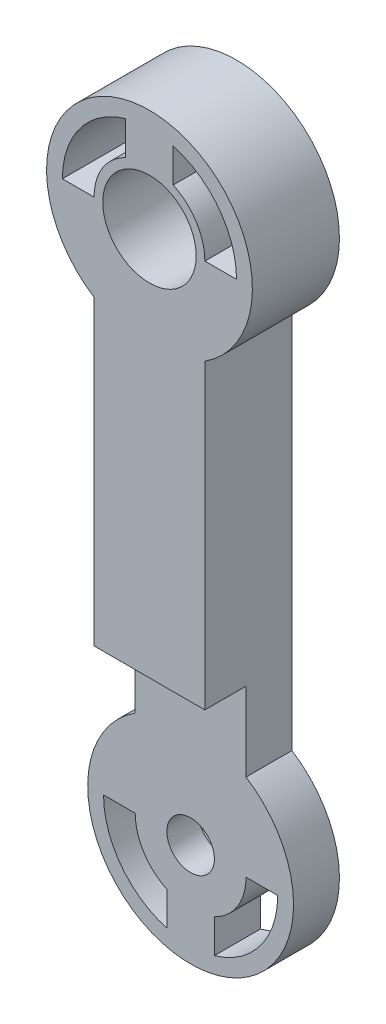
SolidWorks part; units mm, degrees
ref_plane "Front Plane" through (0, 0, 0) normal (0, 0, 1) x (1, 0, 0)
ref_plane "Top Plane" through (0, 0, 0) normal (0, 1, 0) x (1, 0, 0)
ref_plane "Right Plane" through (0, 0, 0) normal (1, 0, 0) x (0, 0, -1)
sketch "Sketch1" plane through (0, 0, 0) normal (0, 0, 1) x (1, 0, 0)
  line L0 (0, 0) -> (0, -35) construction
  line L1 (-3.5, 0) -> (-5.5, 0)
  line L2 (3.5, 0) -> (5.5, 0)
  line L3 (0, -17.5) -> (10.3868, -17.5) construction
  line L5 (-1.5, 3.1623) -> (-1.5, 5.2915)
  line L7 (1.5, 3.1623) -> (1.5, 5.2915)
  line L8 (1.5, -38.1623) -> (1.5, -40.2915)
  line L9 (-1.5, -38.1623) -> (-1.5, -40.2915)
  line L10 (3.5, -35) -> (5.5, -35)
  line L11 (-3.5, -35) -> (-5.5, -35)
  line L13 (-3.5, 0) -> (3.5, 0)
  line L14 (-3.5, 0) -> (-3.5, -35)
  line L15 (-3.5, -35) -> (3.5, -35)
  line L16 (3.5, 0) -> (3.5, -35)
  circle A0 centre (0, 0) radius 2.95
  circle A1 centre (0, 0) radius 6.5
  circle A2 centre (0, 0) radius 3.5
  circle A3 centre (0, 0) radius 5.5
  circle A4 centre (0, -35) radius 5.5
  circle A5 centre (0, -35) radius 3.5
  circle A6 centre (0, -35) radius 6.5
  circle A7 centre (0, -35) radius 2.95
  dimension "D1" = 5.9
  dimension "D2" = 13
  dimension "D3" = 11
  dimension "D4" = 7
  dimension "D5" = 35
extrude "Boss-Extrude1" add sketch "Sketch1" along normal blind 3.7 contours L14 A6 L16 A1 | A3 L16 A1 L14 | L14 A3 L16 A2 | A3 L14 A1 L16 | A6 L14 A4 L16 | A6 L16 A4 L14 | L14 A5 L16 A4 | A4 L11 L14 | A4 L16 L10 | L15 A7 A5 | L15 A7 A5 | L7 A3 L5 A2 | L1 A3 L14 | L16 A3 L2 | L13 A2 A0 | L13 A2 A0 | L8 A5 L9 A4 region at (-4.3139, -1.6382, 0) region at (-2.8919, 1.829, 0) region at (0, -3.8245, 0) region at (-3.225, -0.0783, 0) region at (-5.1348, -2.4206, 0) region at (0, -5.6156, 0) region at (0, 4.4089, 0) region at (4.3139, -1.6382, 0) region at (0, -17.5, 0) region at (0, -29.3844, 0) region at (-3.6768, -30.1401, 0) region at (0, -31.1755, 0) region at (-4.3139, -33.3618, 0) region at (0, -31.5783, 0) region at (-3.225, -35.0783, 0) region at (4.3139, -33.3618, 0) region at (0, -39.4089, 0)
sketch "Sketch2" plane through (0, 0, 0) normal (1, 0, 0) x (0, 0, -1)
  line L0 (0, 0) -> (0, -24.55) construction
  line L1 (0, -5.4772) -> (0, -29.5228) construction
  line L2 (-3.7, -5.4772) -> (-3.7, -29.5228) construction
  line L3 (-3.7, -24.55) -> (-3.1, -24.55)
  line L4 (-3.7, -24.55) -> (-3.7, -41.5)
  line L5 (-3.7, -41.5) -> (-3.1, -41.5)
  line L6 (-3.1, -24.55) -> (-3.1, -41.5)
  line L7 (-3.7, -41.5) -> (0, -41.5) construction
  dimension "D1" = 24.55
  dimension "D2" = 0.6
extrude "Cut-Extrude1" cut sketch "Sketch2" against normal blind 10 and the other way blind 10
sketch "Sketch3" plane through (0, 0, 0) normal (0, 0, -1) x (-1, 0, 0)
  circle A0 centre (0, -35) radius 2.95
  circle A1 centre (0, -35) radius 1.5
  dimension "D1" = 3
extrude "Boss-Extrude2" add sketch "Sketch3" against normal blind 3.1
sketch "Sketch4" plane through (0, 0, 0) normal (0, 0, -1) x (-1, 0, 0)
  circle A0 centre (0, -35) radius 2.5
  dimension "D1" = 5
extrude "Cut-Extrude2" cut sketch "Sketch4" against normal blind 1.5
sketch "Sketch5" plane through (0, 0, 3.1) normal (0, 0, 1) x (1, 0, 0)
  line L1 (-3.5, -24.55) -> (3.5, -24.55)
  line L2 (-3.5, -24.55) -> (-3.5, -29.5228)
  line L4 (3.5, -24.55) -> (3.5, -29.5228)
  line L5 (-5.5, -35) -> (-3.5, -35)
  line L8 (-1.5, -38.1623) -> (-1.5, -40.2915)
  line L9 (5.5, -35) -> (3.5, -35)
  line L12 (1.5, -38.1623) -> (1.5, -40.2915)
  circle A0 centre (0, -35) radius 1.5
  circle A1 centre (0, -35) radius 6.5
  circle A2 centre (0, -35) radius 3.5
  arc A3 (-5.5, -35) -> (5.5, -35) centre (0, -35) ccw
  line M2 (3.5, -35) -> (5.5, -35)
  line M4 (1.5, -40.2915) -> (1.5, -38.1623)
  arc M5 (1.5, -38.1623) -> (3.5, -35) centre (0, -35) ccw
  arc M6 (-3.5, -35) -> (-1.5, -38.1623) centre (0, -35) ccw
  line M7 (-1.5, -38.1623) -> (-1.5, -40.2915)
  line M9 (-5.5, -35) -> (-3.5, -35)
  line M10 (-3.5, -24.55) -> (-3.5, -29.5228)
  line M12 (3.5, -29.5228) -> (3.5, -24.55)
  line M13 (3.5, -24.55) -> (-3.5, -24.55)
  circle M14 centre (0, -35) radius 1.5
extrude "Boss-Extrude3" add sketch "Sketch5" along normal blind 0.4 contours A1 M12 M13 M10 | A3 A2 M2 M9 | A2 M5 M6 M14 | A3 A2 M7 M4 region at (0, -26.7003, 3.1) region at (0, -28.6838, 3.1) region at (0, -31.599, 3.1) region at (0, -39.4089, 3.1)
sketch "Sketch6" plane through (0, 0, 3.7) normal (0, 0, 1) x (1, 0, 0)
  line L0 (-1.5, 5.2915) -> (-1.5, 3.1623)
  line L2 (-3.5, -5.4772) -> (-3.5, -24.55)
  line L3 (-3.5, -24.55) -> (3.5, -24.55)
  line L4 (3.5, -5.4772) -> (3.5, -24.55)
  line L5 (1.5, 5.2915) -> (1.5, 3.1623)
  line L6 (3.5, 0) -> (5.5, 0)
  line L7 (-5.5, 0) -> (-3.5, 0)
  circle A0 centre (0, 0) radius 2.95
  arc A1 (3.5, -5.4772) -> (-3.5, -5.4772) centre (0, 0) ccw
  arc A2 (-1.5, 5.2915) -> (-5.5, 0) centre (0, 0) ccw
  arc A3 (-1.5, 3.1623) -> (-3.5, 0) centre (0, 0) ccw
  arc A4 (3.5, 0) -> (1.5, 3.1623) centre (0, 0) ccw
  arc A5 (5.5, 0) -> (1.5, 5.2915) centre (0, 0) ccw
extrude "Boss-Extrude4" add sketch "Sketch6" along normal blind 2.4
sketch "Sketch7" plane through (0, 0, 0) normal (0, 0, 1) x (1, 0, 0)
  line L1 (12.005, 7.8195) -> (-10.0995, 7.8195)
  line L2 (12.005, 7.8195) -> (12.005, -42.7273)
  line L3 (12.005, -42.7273) -> (-10.0995, -42.7273)
  line L4 (-10.0995, 7.8195) -> (-10.0995, -42.7273)
extrude "Cut-Extrude3" cut sketch "Sketch7" along normal blind 0.6
